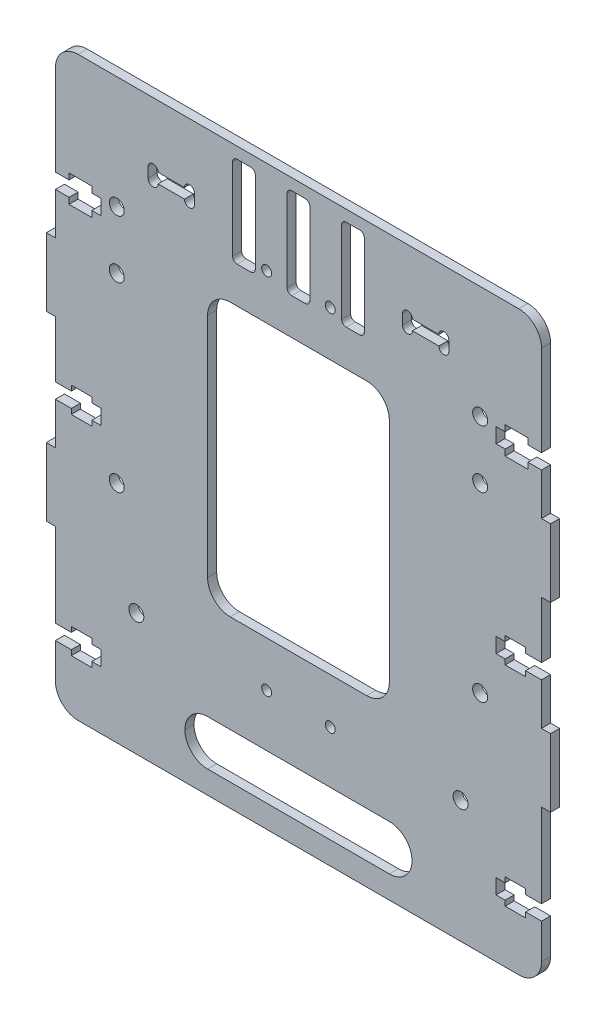
SolidWorks part; units mm, degrees
material "A-玻璃纤维"
ref_plane "前视基准面" through (0, 0, 0) normal (0, 0, 1) x (1, 0, 0)
ref_plane "上视基准面" through (0, 0, 0) normal (0, 1, 0) x (1, 0, 0)
ref_plane "右视基准面" through (0, 0, 0) normal (1, 0, 0) x (0, 0, -1)
sketch "草图1" plane through (0, 0, 0) normal (0, 0, 1) x (1, 0, 0)
  line L1 (54, -7.5) -> (-54, -7.5) construction
  line L2 (54, -7.5) -> (54, 7.5) construction
  line L3 (54, 7.5) -> (-54, 7.5) construction
  line L4 (-54, -7.5) -> (-54, 7.5) construction
  line L5 (54, -7.5) -> (-54, 7.5) construction
  line L6 (54, 7.5) -> (-54, -7.5) construction
  line L7 (53.5, -12.5) -> (-53.5, -12.5)
  line L8 (53.5, -12.5) -> (53.5, 12.5)
  line L9 (53.5, 12.5) -> (-53.5, 12.5)
  line L10 (-53.5, -12.5) -> (-53.5, 12.5)
  line L11 (53.5, -12.5) -> (-53.5, 12.5) construction
  line L12 (53.5, 12.5) -> (-53.5, -12.5) construction
  point P0 (0, 0)
  point P10 (0, 0)
  dimension "D1" = 108
  dimension "D2" = 15
  dimension "D7" = 25
  dimension "D8" = 107
extrude "凸台-拉伸1" add sketch "草图1" along normal blind 2
sketch "草图3" plane through (0, -12.5, 0) normal (0, -1, 0) x (1, 0, 0)
  line L4 (-53.5, 0) -> (53.5, 0)
  line L5 (53.5, 0) -> (53.5, 2)
  line L6 (53.5, 2) -> (-53.5, 2)
  line L7 (-53.5, 2) -> (-53.5, 0)
  line L8 (-53.5, 0) -> (53.5, 0)
  line L9 (53.5, 0) -> (53.5, 2)
  line L10 (53.5, 2) -> (-53.5, 2)
  line L11 (-53.5, 2) -> (-53.5, 0)
  dimension "D1" = 0
extrude "凸台-拉伸2" add sketch "草图3" along normal blind 10
sketch "草图4" plane through (0, 0, 2) normal (0, 0, 1) x (1, 0, 0)
  line L0 (-28, -2.3) -> (-28, -8.6814) construction
  line L1 (-25.1, -3.4) -> (-30.9, -3.4)
  line L2 (-22.9, -3.4) -> (-22.9, -1.2)
  line L3 (-25.1, -1.2) -> (-30.9, -1.2)
  line L4 (-33.1, -3.4) -> (-33.1, -1.2)
  line L5 (-22.9, -3.4) -> (-33.1, -1.2) construction
  line L6 (-22.9, -1.2) -> (-33.1, -3.4) construction
  line L7 (0, -34.9979) -> (0, 1.2592) construction
  line L8 (22.9, -3.4) -> (22.9, -1.2)
  line L9 (25.1, -1.2) -> (30.9, -1.2)
  line L10 (33.1, -3.4) -> (33.1, -1.2)
  line L11 (25.1, -3.4) -> (30.9, -3.4)
  arc A0 (-30.9, -1.2) -> (-33.1, -1.2) centre (-32, -1.2) ccw
  arc A1 (-33.1, -3.4) -> (-30.9, -3.4) centre (-32, -3.4) ccw
  arc A2 (-22.9, -3.4) -> (-25.1, -3.4) centre (-24, -3.4) cw
  arc A3 (-25.1, -1.2) -> (-22.9, -1.2) centre (-24, -1.2) cw
  arc A4 (22.9, -3.4) -> (25.1, -3.4) centre (24, -3.4) ccw
  arc A5 (25.1, -1.2) -> (22.9, -1.2) centre (24, -1.2) ccw
  arc A6 (30.9, -1.2) -> (33.1, -1.2) centre (32, -1.2) cw
  arc A7 (33.1, -3.4) -> (30.9, -3.4) centre (32, -3.4) cw
  point P0 (-28, -2.3)
  point P5 (28, -2.3)
  dimension "D3" = 2.2
  dimension "D4" = 2.2
  dimension "D7" = 2.3
  dimension "D1" = 2.2
  dimension "D2" = 10.2
  dimension "D5" = 28
  dimension "D6" = 28
extrude "切除-拉伸2" cut sketch "草图4" against normal blind 2
sketch "草图5" plane through (0, 0, 2) normal (0, 0, 1) x (1, 0, 0)
  line L0 (53.5, -22.5) -> (53.5, 12.5) construction
  line L1 (53.5, 20.6779) -> (46.89, 20.6779)
  line L2 (53.5, 20.6779) -> (53.5, -29.1708)
  line L3 (53.5, -29.1708) -> (46.89, -29.1708)
  line L4 (46.89, 20.6779) -> (46.89, -29.1708)
  line L5 (-53.5, 23.2283) -> (-46.89, 23.2283)
  line L6 (-53.5, 23.2283) -> (-53.5, -31.8371)
  line L7 (-53.5, -31.8371) -> (-46.89, -31.8371)
  line L8 (-46.89, 23.2283) -> (-46.89, -31.8371)
  line L9 (-53.5, 12.5) -> (-53.5, -22.5) construction
  dimension "D1" = 6.61
  dimension "D2" = 6.61
sketch "草图6" plane through (0, 0, 0) normal (0, 0, -1) x (-1, 0, 0)
  circle A0 centre (-40, -9.3) radius 1.65
  circle A1 centre (40, -9.3) radius 1.65
  arc A3 (-25.1, -3.4) -> (-22.9, -3.4) centre (-24, -3.4) ccw construction
  dimension "D1" = 3.3
  dimension "D2" = 3.3
  dimension "D3" = 5.9
  dimension "D4" = 40
  dimension "D5" = 40
extrude "切除-拉伸4" cut sketch "草图6" against normal blind 10
sketch "草图7" plane through (0, -22.5, 0) normal (0, -1, 0) x (1, 0, 0)
  line L4 (-53.5, 2) -> (-53.5, 0)
  line L7 (-53.5, 0) -> (53.5, 0)
  line L11 (-53.5, 0) -> (53.5, 0)
  line L14 (53.5, 2) -> (-53.5, 2)
  line L15 (53.5, 2) -> (-53.5, 2)
  line L16 (-53.5, 2) -> (-53.5, 0)
  line L18 (53.5, 0) -> (53.5, 2)
  line L19 (53.5, 0) -> (53.5, 2)
  dimension "D1" = 0
extrude "凸台-拉伸3" add sketch "草图7" along normal blind 100
sketch "草图8" plane through (0, 0, 0) normal (0, 0, -1) x (-1, 0, 0)
  line L1 (7, -88) -> (-7, -88) construction
  line L2 (7, -88) -> (7, -8) construction
  line L3 (7, -8) -> (-7, -8) construction
  line L4 (-7, -88) -> (-7, -8) construction
  line L5 (7, -88) -> (-7, -8) construction
  line L6 (7, -8) -> (-7, -88) construction
  circle A0 centre (-7, -8) radius 1.1
  circle A1 centre (7, -8) radius 1.1
  circle A2 centre (-7, -88) radius 1.1
  circle A3 centre (7, -88) radius 1.1
  point P0 (0, -48)
  dimension "D4" = 2.2
  dimension "D5" = 2.2
  dimension "D6" = 2.2
  dimension "D7" = 2.2
  dimension "D1" = 80
  dimension "D2" = 14
  dimension "D3" = 48
extrude "切除-拉伸5" cut sketch "草图8" against normal blind 50
sketch "草图9" plane through (0, 0, 0) normal (0, 0, -1) x (-1, 0, 0)
  line L1 (20, -78) -> (-20, -78)
  line L2 (20, -78) -> (20, -18)
  line L3 (20, -18) -> (-20, -18)
  line L4 (-20, -78) -> (-20, -18)
  line L5 (20, -78) -> (-20, -18) construction
  line L6 (20, -18) -> (-20, -78) construction
  point P0 (0, -48)
  dimension "D1" = 60
  dimension "D2" = 40
  dimension "D3" = 48
extrude "切除-拉伸6" cut sketch "草图9" against normal blind 50
fillet "圆角3" radius 5 4 edges at (20, -78, 1) (-20, -78, 1) (-20, -18, 1) (20, -18, 1)
sketch "草图10" plane through (0, 0, 0) normal (0, 0, -1) x (-1, 0, 0)
  line L0 (-53.5, 12.5) -> (-53.5, -122.5) construction
  line L1 (-53.5, -25) -> (-55.5, -25)
  line L2 (-53.5, -25) -> (-53.5, -40)
  line L3 (-53.5, -40) -> (-55.5, -40)
  line L4 (-55.5, -25) -> (-55.5, -40)
  line L5 (53.5, -122.5) -> (53.5, 12.5) construction
  line L6 (-53.5, -65) -> (-55.5, -65)
  line L7 (-53.5, -65) -> (-53.5, -80)
  line L8 (-53.5, -80) -> (-55.5, -80)
  line L9 (-55.5, -65) -> (-55.5, -80)
  line L10 (53.5, -25) -> (55.5, -25)
  line L11 (53.5, -25) -> (53.5, -40)
  line L12 (53.5, -40) -> (55.5, -40)
  line L13 (55.5, -25) -> (55.5, -40)
  line L15 (53.5, -65) -> (55.5, -65)
  line L16 (53.5, -65) -> (53.5, -80)
  line L17 (53.5, -80) -> (55.5, -80)
  line L18 (55.5, -65) -> (55.5, -80)
  dimension "D1" = 15
  dimension "D2" = 2
  dimension "D3" = 15
  dimension "D4" = 2
  dimension "D5" = 15
  dimension "D6" = 2
  dimension "D7" = 15
  dimension "D8" = 2
  dimension "D9" = 25
  dimension "D10" = 25
extrude "凸台-拉伸4" add sketch "草图10" against normal up to surface (2 mm away) up to face at (0, -48, 2)
sketch "草图11" plane through (0, 0, 2) normal (0, 0, 1) x (1, 0, 0)
  line L0 (-53.5, -25) -> (-53.5, 12.5) construction
  line L1 (-53.5, -15.75) -> (-50.5, -15.75)
  line L2 (-53.5, -15.75) -> (-53.5, -12.45)
  line L3 (-53.5, -12.45) -> (-50.5, -12.45)
  line L4 (-43.5, -15.75) -> (-43.5, -12.45)
  line L5 (-53.5, -65) -> (-53.5, -40) construction
  line L6 (-53.5, -52.45) -> (-50, -52.45)
  line L7 (-53.5, -52.45) -> (-53.5, -55.75)
  line L8 (-53.5, -55.75) -> (-50, -55.75)
  line L9 (-43.5, -52.45) -> (-43.5, -55.75)
  line L10 (-53.5, -122.5) -> (-53.5, -80) construction
  line L11 (-53.5, -98.45) -> (-50, -98.45)
  line L12 (-53.5, -98.45) -> (-53.5, -101.75)
  line L13 (-53.5, -101.75) -> (-50, -101.75)
  line L14 (-43.5, -98.45) -> (-43.5, -101.75)
  line L15 (-55.5, -25) -> (-53.5, -25) construction
  line L16 (-45.5, -102.9) -> (-50, -102.9)
  line L17 (-45.5, -102.9) -> (-45.5, -101.75)
  line L18 (-45.5, -97.3) -> (-50, -97.3)
  line L19 (-50, -102.9) -> (-50, -101.75)
  line L20 (-45.5, -102.9) -> (-50, -97.3) construction
  line L21 (-45.5, -97.3) -> (-50, -102.9) construction
  line L22 (-45.5, -56.9) -> (-50, -56.9)
  line L23 (-45.5, -56.9) -> (-45.5, -55.75)
  line L24 (-45.5, -51.3) -> (-50, -51.3)
  line L25 (-50, -56.9) -> (-50, -55.75)
  line L26 (-45.5, -56.9) -> (-50, -51.3) construction
  line L27 (-45.5, -51.3) -> (-49.0759, -55.75) construction
  line L28 (-45.5, -17.1) -> (-50.5, -17.1)
  line L29 (-45.5, -17.1) -> (-45.5, -15.75)
  line L30 (-45.5, -11.1) -> (-50.5, -11.1)
  line L31 (-50.5, -17.1) -> (-50.5, -15.75)
  line L32 (-45.5, -17.1) -> (-50.5, -11.1) construction
  line L33 (-45.5, -11.1) -> (-50.5, -17.1) construction
  line L34 (-55.5, -65) -> (-53.5, -65) construction
  line L35 (-53.5, -80) -> (-55.5, -80) construction
  line L36 (-45.5, -12.45) -> (-43.5, -12.45)
  line L37 (-50.5, -12.45) -> (-50.5, -11.1)
  line L38 (-45.5, -12.45) -> (-45.5, -11.1)
  line L39 (-45.5, -15.75) -> (-43.5, -15.75)
  line L40 (-45.5, -52.45) -> (-43.5, -52.45)
  line L41 (-45.5, -55.75) -> (-43.5, -55.75)
  line L42 (-50, -52.45) -> (-50, -51.3)
  line L43 (-45.5, -52.45) -> (-45.5, -51.3)
  line L44 (-45.5, -98.45) -> (-43.5, -98.45)
  line L45 (-50, -98.45) -> (-50, -97.3)
  line L46 (-45.5, -101.75) -> (-43.5, -101.75)
  line L47 (-45.5, -98.45) -> (-45.5, -97.3)
  line L48 (0, 0) -> (0, -65.1332) construction
  line L49 (45.5, -102.9) -> (45.5, -101.75)
  line L50 (45.5, -101.75) -> (43.5, -101.75)
  line L51 (43.5, -98.45) -> (43.5, -101.75)
  line L52 (45.5, -98.45) -> (43.5, -98.45)
  line L53 (45.5, -98.45) -> (45.5, -97.3)
  line L54 (45.5, -97.3) -> (50, -97.3)
  line L55 (50, -98.45) -> (50, -97.3)
  line L56 (53.5, -98.45) -> (50, -98.45)
  line L57 (53.5, -98.45) -> (53.5, -101.75)
  line L58 (53.5, -101.75) -> (50, -101.75)
  line L59 (50, -102.9) -> (50, -101.75)
  line L60 (45.5, -102.9) -> (50, -102.9)
  line L61 (45.5, -56.9) -> (45.5, -55.75)
  line L62 (45.5, -55.75) -> (43.5, -55.75)
  line L63 (43.5, -52.45) -> (43.5, -55.75)
  line L64 (45.5, -52.45) -> (43.5, -52.45)
  line L65 (45.5, -52.45) -> (45.5, -51.3)
  line L66 (45.5, -51.3) -> (50, -51.3)
  line L67 (50, -52.45) -> (50, -51.3)
  line L68 (53.5, -52.45) -> (50, -52.45)
  line L69 (53.5, -52.45) -> (53.5, -55.75)
  line L70 (53.5, -55.75) -> (50, -55.75)
  line L71 (50, -56.9) -> (50, -55.75)
  line L72 (45.5, -56.9) -> (50, -56.9)
  line L73 (45.5, -17.1) -> (45.5, -15.75)
  line L74 (45.5, -17.1) -> (50.5, -17.1)
  line L75 (50.5, -17.1) -> (50.5, -15.75)
  line L76 (53.5, -15.75) -> (50.5, -15.75)
  line L77 (53.5, -15.75) -> (53.5, -12.45)
  line L78 (53.5, -12.45) -> (50.5, -12.45)
  line L79 (50.5, -12.45) -> (50.5, -11.1)
  line L80 (45.5, -11.1) -> (50.5, -11.1)
  line L81 (45.5, -12.45) -> (45.5, -11.1)
  line L82 (45.5, -12.45) -> (43.5, -12.45)
  line L83 (43.5, -15.75) -> (43.5, -12.45)
  line L84 (45.5, -15.75) -> (43.5, -15.75)
  point P18 (-47.75, -100.1)
  point P24 (-43.5, -100.1)
  point P25 (-47.75, -54.1)
  point P30 (-48, -14.1)
  point P36 (-43.5, -14.1)
  point P42 (-43.5, -54.1)
  point P47 (-53.5, -100.1)
  dimension "D1" = 3.3
  dimension "D2" = 10
  dimension "D3" = 3.3
  dimension "D4" = 10
  dimension "D5" = 3.3
  dimension "D6" = 10
  dimension "D7" = 5.6
  dimension "D8" = 4.5
  dimension "D9" = 5.6
  dimension "D10" = 4.5
  dimension "D11" = 6
  dimension "D12" = 5
  dimension "D13" = 2
  dimension "D14" = 10.9
  dimension "D15" = 10.9
  dimension "D16" = 20.1
extrude "切除-拉伸7" cut sketch "草图11" against normal blind 50
sketch "草图12" plane through (0, 0, 2) normal (0, 0, 1) x (1, 0, 0)
  line L0 (0, 0) -> (0, -88.4525) construction
  circle A0 centre (-35.69, -87.6) radius 1.65
  circle A1 centre (-7, -88) radius 1.1 construction
  circle A2 centre (35.69, -87.6) radius 1.65
  dimension "D1" = 3.3
  dimension "D3" = 28.69
  dimension "D2" = 0.4
extrude "切除-拉伸8" cut sketch "草图12" against normal blind 50
sketch "草图13" plane through (0, 0, 2) normal (0, 0, 1) x (1, 0, 0)
  line L1 (40, -65) -> (-40, -65) construction
  line L2 (40, -65) -> (40, -25) construction
  line L3 (40, -25) -> (-40, -25) construction
  line L4 (-40, -65) -> (-40, -25) construction
  line L5 (40, -65) -> (-40, -25) construction
  line L6 (40, -25) -> (-40, -65) construction
  circle A0 centre (-40, -25) radius 1.65
  circle A1 centre (40, -25) radius 1.65
  circle A2 centre (40, -65) radius 1.65
  circle A3 centre (-40, -65) radius 1.65
  point P0 (0, -45)
  dimension "D4" = 3.3
  dimension "D5" = 3.3
  dimension "D6" = 3.3
  dimension "D7" = 3.3
  dimension "D1" = 40
  dimension "D2" = 80
  dimension "D3" = 45
extrude "切除-拉伸9" cut sketch "草图13" against normal blind 10
sketch "草图14" plane through (0, 0, 2) normal (0, 0, 1) x (1, 0, 0)
  circle A0 centre (-40, -12.3) radius 1.65
  circle A1 centre (40, -12.3) radius 1.65
  circle A2 centre (-40, -9.3) radius 1.65 construction
  circle A3 centre (40, -9.3) radius 1.65 construction
  dimension "D1" = 3.3
  dimension "D2" = 3.3
  dimension "D3" = 3
  dimension "D4" = 3
extrude "切除-拉伸10" cut sketch "草图14" against normal blind 10
sketch "草图15" plane through (0, 0, 2) normal (0, 0, 1) x (1, 0, 0)
  arc A0 (-39.3126, -20.5) -> (-40.6874, -20.5) centre (-40, -12.3) ccw
  arc A1 (-39.3126, -20.5) -> (-40.6874, -20.5) centre (-40, -9.3) ccw
  arc A2 (40.1378, -13.9442) -> (39.8622, -13.9442) centre (40, -9.3) ccw
  arc A3 (40.1378, -13.9442) -> (39.8622, -13.9442) centre (40, -12.3) ccw
extrude "凸台-拉伸5" [suppressed] add sketch "草图15" against normal up to surface (2 mm away)
sketch "草图16" plane through (0, 0, 2) normal (0, 0, 1) x (1, 0, 0)
  line L0 (53.5, -101.75) -> (53.5, -122.5) construction
  line L1 (-53.5, -122.5) -> (53.5, -122.5)
  line L2 (-53.5, -122.5) -> (-53.5, -114.5)
  line L3 (-53.5, -114.5) -> (53.5, -114.5)
  line L4 (53.5, -122.5) -> (53.5, -114.5)
  line L5 (-53.5, -101.75) -> (-53.5, -122.5) construction
  dimension "D1" = 8
extrude "切除-拉伸11" cut sketch "草图16" against normal blind 10
fillet "圆角4" radius 5 4 edges at (-53.5, -114.5, 1) (53.5, -114.5, 1) (53.5, 12.5, 1) (-53.5, 12.5, 1)
sketch "草图17" plane through (0, 0, 2) normal (0, 0, 1) x (1, 0, 0)
  line L0 (0, 0) -> (0, -54.3487) construction
  arc A0 (-39.3126, -10.8) -> (-40.6874, -10.8) centre (-40, -9.3) ccw
  arc A1 (-39.3126, -10.8) -> (-40.6874, -10.8) centre (-40, -12.3) ccw
  arc A3 (39.3126, -10.8) -> (40.6874, -10.8) centre (40, -12.3) cw
  arc A4 (39.3126, -10.8) -> (40.6874, -10.8) centre (40, -9.3) cw
extrude "凸台-拉伸6" add sketch "草图17" against normal up to surface (2 mm away) up to face at (-38.35, -25, 0)
sketch "草图18" plane through (0, 0, 2) normal (0, 0, 1) x (1, 0, 0)
  line L0 (9.5, -9) -> (9.5, 9)
  line L1 (-1.5, -10) -> (1.5, -10)
  line L2 (-2.5, -9) -> (-2.5, 9)
  line L3 (-1.5, 10) -> (1.5, 10)
  line L4 (2.5, -9) -> (2.5, 9)
  line L5 (-2.5, -10) -> (2.5, 10) construction
  line L6 (-2.5, 10) -> (2.5, -10) construction
  line L7 (10.5, -10) -> (13.5, -10)
  line L8 (14.5, -9) -> (14.5, 9)
  line L9 (10.5, 10) -> (13.5, 10)
  line L14 (-14.5, -9) -> (-14.5, 9)
  line L15 (-13.5, -10) -> (-10.5, -10)
  line L16 (-9.5, -9) -> (-9.5, 9)
  line L17 (-13.5, 10) -> (-10.5, 10)
  line L22 (21.5, -9) -> (21.5, 9) [skipped]
  line L23 (22.5, 10) -> (25.5, 10) [skipped]
  line L24 (26.5, -9) -> (26.5, 9) [skipped]
  line L25 (22.5, -10) -> (25.5, -10) [skipped]
  line L26 (-26.5, -9) -> (-26.5, 9) [skipped]
  line L27 (-25.5, 10) -> (-22.5, 10) [skipped]
  line L28 (-21.5, -9) -> (-21.5, 9) [skipped]
  line L29 (-25.5, -10) -> (-22.5, -10) [skipped]
  arc A0 (-1.5, -10) -> (-2.5, -9) centre (-1.5, -9) cw
  arc A1 (1.5, -10) -> (2.5, -9) centre (1.5, -9) ccw
  arc A2 (1.5, 10) -> (2.5, 9) centre (1.5, 9) cw
  arc A3 (-2.5, 9) -> (-1.5, 10) centre (-1.5, 9) cw
  arc A4 (9.5, 9) -> (10.5, 10) centre (10.5, 9) cw
  arc A5 (10.5, -10) -> (9.5, -9) centre (10.5, -9) cw
  arc A6 (13.5, -10) -> (14.5, -9) centre (13.5, -9) ccw
  arc A7 (13.5, 10) -> (14.5, 9) centre (13.5, 9) cw
  arc A12 (-14.5, 9) -> (-13.5, 10) centre (-13.5, 9) cw
  arc A13 (-13.5, -10) -> (-14.5, -9) centre (-13.5, -9) cw
  arc A14 (-10.5, -10) -> (-9.5, -9) centre (-10.5, -9) ccw
  arc A15 (-10.5, 10) -> (-9.5, 9) centre (-10.5, 9) cw
  arc A20 (21.5, 9) -> (22.5, 10) centre (22.5, 9) cw [skipped]
  arc A21 (25.5, 10) -> (26.5, 9) centre (25.5, 9) cw [skipped]
  arc A22 (25.5, -10) -> (26.5, -9) centre (25.5, -9) ccw [skipped]
  arc A23 (22.5, -10) -> (21.5, -9) centre (22.5, -9) cw [skipped]
  arc A24 (-26.5, 9) -> (-25.5, 10) centre (-25.5, 9) cw [skipped]
  arc A25 (-22.5, 10) -> (-21.5, 9) centre (-22.5, 9) cw [skipped]
  arc A26 (-22.5, -10) -> (-21.5, -9) centre (-22.5, -9) ccw [skipped]
  arc A27 (-25.5, -10) -> (-26.5, -9) centre (-25.5, -9) cw [skipped]
  point P0 (0, 0)
  dimension "D3" = 1
  dimension "D1" = 20
  dimension "D2" = 5
  dimension "D6" = 12
  dimension "D7" = 12
  dimension "D4" = 3
  dimension "D5" = 3
extrude "切除-拉伸12" cut sketch "草图18" against normal blind 10
sketch "草图19" plane through (0, 0, 0) normal (0, 0, -1) x (-1, 0, 0)
  line L0 (-48.5, -114.5) -> (48.5, -114.5) construction
  line L1 (25, -99.5) -> (-25, -99.5)
  line L2 (25, -99.5) -> (25, -129.5)
  line L3 (25, -129.5) -> (-25, -129.5)
  line L4 (-25, -99.5) -> (-25, -129.5)
  line L5 (25, -99.5) -> (-25, -129.5) construction
  line L6 (25, -129.5) -> (-25, -99.5) construction
  point P0 (0, -114.5)
  dimension "D1" = 30
  dimension "D2" = 50
extrude "切除-拉伸13" cut sketch "草图19" against normal blind 10
fillet "圆角5" radius 5 4 edges at (-25, -114.5, 1) (-25, -99.5, 1) (25, -114.5, 1) (25, -99.5, 1)
sketch "草图20" plane through (0, 0, 2) normal (0, 0, 1) x (1, 0, 0)
  line L0 (-30, -114.5) -> (-48.5, -114.5) construction
  line L1 (-38.094, -114.5) -> (35.856, -114.5)
  line L2 (-38.094, -114.5) -> (-38.094, -109.5)
  line L3 (-38.094, -109.5) -> (35.856, -109.5)
  line L4 (35.856, -114.5) -> (35.856, -109.5)
  dimension "D1" = 5
  dimension "D2" = 73.95
extrude "凸台-拉伸8" add sketch "草图20" against normal up to surface (2 mm away) up to face at (-12, 0, 0)
fillet "圆角6" radius 5 2 edges at (25, -109.5, 1) (-25, -109.5, 1)
